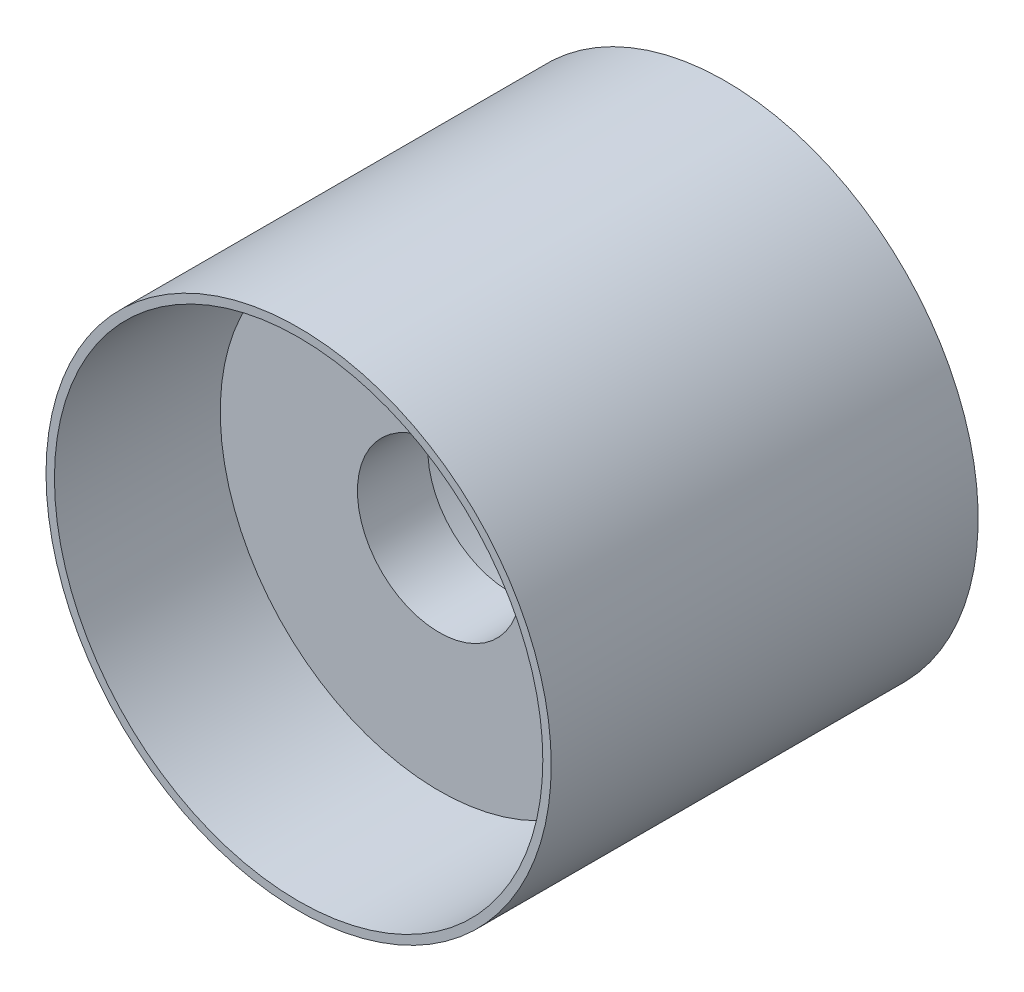
SolidWorks part; units mm, degrees
ref_plane "Front Plane" through (0, 0, 0) normal (0, 0, 1) x (1, 0, 0)
ref_plane "Top Plane" through (0, 0, 0) normal (0, 1, 0) x (1, 0, 0)
ref_plane "Right Plane" through (0, 0, 0) normal (1, 0, 0) x (0, 0, -1)
sketch "Sketch3" plane through (0, 0, 0) normal (0, 1, 0) x (1, 0, 0)
  line L0 (0, -92.0641) -> (0, 41.4532) construction
  line L1 (0, 41.4532) -> (260, -92.0641)
  line L2 (260, -92.0641) -> (0, -92.0641)
  line L3 (0, -92.0641) -> (0, 41.4532)
  dimension ".26" = 260
revolve "Revolve2" add sketch "Sketch3" angle 360 about L0
sketch "Sketch5" plane through (0, 0, 0) normal (0, 0, 1) x (1, 0, 0)
  circle A0 centre (0, 0) radius 300
  circle A1 centre (0, 0) radius 290
  dimension "D1" = 580
extrude "Boss-Extrude2" add sketch "Sketch5" against normal blind 238 and the other way blind 259 separate body
sketch "Sketch6" plane through (0, 0, 0) normal (0, 0, 1) x (1, 0, 0)
  circle A0 centre (0, 0) radius 97.1024
  dimension "D1" = 194.2047
extrude "Cut-Extrude1" cut sketch "Sketch6" along normal blind 186 and the other way blind 76
ref_plane "Plane1" through (0, 0, 90) normal (0, 0, 1) x (1, 0, 0)
sketch "Sketch7" plane through (0, 0, -238) normal (0, 0, -1) x (-1, 0, 0)
  circle A0 centre (0, 0) radius 300
extrude "Boss-Extrude5" add sketch "Sketch7" along normal blind 10
sketch "Sketch8" plane through (0, 0, -248) normal (0, 0, -1) x (-1, 0, 0)
  line L0 (0, 25) -> (0, -25) construction
  line L1 (-79.0214, 25) -> (-142.8038, 25)
  line L2 (-142.8038, 25) -> (-142.8038, -25)
  line L3 (-142.8038, -25) -> (-79.0214, -25)
  line L4 (-79.0214, -25) -> (-79.0214, 25)
  line L5 (-142.8038, 25) -> (142.8038, 25) construction
  line L6 (142.8038, 25) -> (79.0214, 25)
  line L7 (79.0214, 25) -> (79.0214, -25)
  line L8 (79.0214, -25) -> (142.8038, -25)
  line L9 (142.8038, -25) -> (142.8038, 25)
  point P0 (0, 0)
  point P1 (0, -25)
  point P2 (0, 25)
  dimension "D1" = 50
  dimension "D2" = 25
  dimension "D3" = 142.8038
  dimension "D4" = 142.8038
  dimension "D5" = 63.7824
  dimension "D6" = 63.7824
extrude "Boss-Extrude6" add sketch "Sketch8" along normal blind 10
sketch "Sketch9" plane through (0, 0, -258) normal (0, 0, -1) x (-1, 0, 0)
  line L0 (-142.8038, -25) -> (-79.0214, -25) construction
  line L1 (-79.0214, 25) -> (-86.5678, 25)
  line L2 (-79.0214, 25) -> (-79.0214, -25)
  line L3 (-79.0214, -25) -> (-86.5678, -25)
  line L4 (-86.5678, 25) -> (-86.5678, -25)
  dimension "D1" = 7.5464
extrude "Boss-Extrude7" add sketch "Sketch9" along normal blind 80
sketch "Sketch10" plane through (79.0214, 0, 0) normal (-1, 0, 0) x (0, 0, 1)
  line L0 (-338, -25) -> (-248, -25) construction
  line L1 (-338, 25) -> (-330.7379, 25)
  line L2 (-338, 25) -> (-338, -25)
  line L3 (-338, -25) -> (-330.7379, -25)
  line L4 (-330.7379, 25) -> (-330.7379, -25)
  dimension "D1" = 50
sketch "Sketch11" plane through (0, 0, 0) normal (0, 0, 1) x (1, 0, 0)
  line L0 (142.8038, 25) -> (-142.8038, 25) construction
  line L1 (0, 0) -> (0, 25) construction
  point P0 (0, 0)
  point P7 (86.5678, 25)
  point P8 (-86.5678, 25)
  dimension "D1" = 142.8038
  dimension "D2" = 142.8038
  dimension "D3" = 56.236
  dimension "D4" = 86.5678
  dimension "D5" = 86.5678
  dimension "D6" = 173.1356
extrude "Boss-Extrude8" add sketch "Sketch10" along normal blind 158.0427
sketch "Sketch13" plane through (0, 0, -258) normal (0, 0, -1) x (-1, 0, 0)
  line L0 (79.0214, -25) -> (142.8038, -25) construction
  line L1 (79.0214, 25) -> (86.5678, 25)
  line L2 (79.0214, 25) -> (79.0214, -25)
  line L3 (79.0214, -25) -> (86.5678, -25)
  line L4 (86.5678, 25) -> (86.5678, -25)
  dimension "D1" = 7.5464
extrude "Boss-Extrude9" add sketch "Sketch13" along normal blind 80
sketch "Sketch14" plane through (0, 0, -248) normal (0, 0, -1) x (-1, 0, 0)
  point P0 (-79.0214, -25)
  point P1 (79.0214, -25)
  dimension "D1" = 158.0427
fillet "Fillet3" radius 5 16 edges at (86.5678, 0, -258) (142.8038, 0, -258) (114.6858, -25, -258) (114.6858, 25, -258) (86.5678, 25, -298) (86.5678, -25, -298) (86.5678, 0, -338) (0, 25, -338) (0, -25, -338) (-114.6858, 25, -258) (-142.8038, 0, -258) (-114.6858, -25, -258) (-86.5678, 0, -258) (-79.0214, 0, -330.7379) (-86.5678, -25, -298) (-86.5678, 25, -298)
